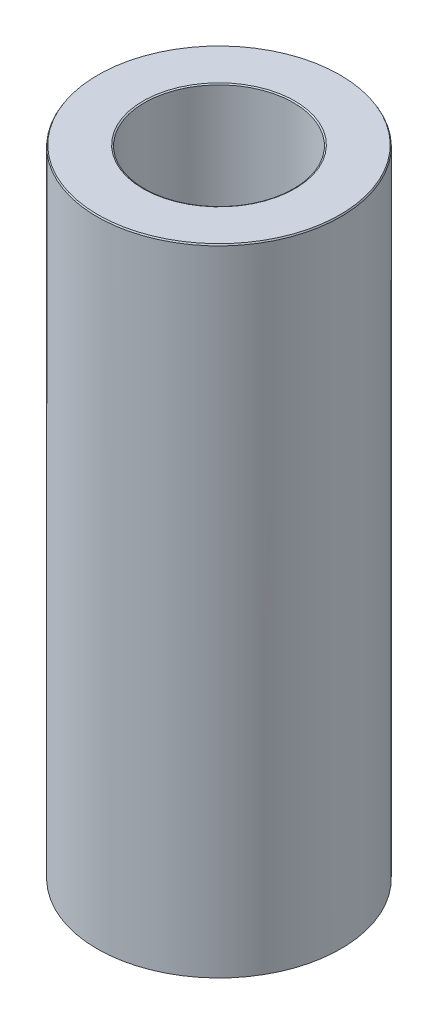
SolidWorks part; units mm, degrees
ref_plane "Front Plane" through (0, 0, 0) normal (0, 0, 1) x (1, 0, 0)
ref_plane "Top Plane" through (0, 0, 0) normal (0, 1, 0) x (1, 0, 0)
ref_plane "Right Plane" through (0, 0, 0) normal (1, 0, 0) x (0, 0, -1)
sketch "Sketch1" plane through (0, 0, 0) normal (0, 1, 0) x (1, 0, 0)
  circle A0 centre (0, 0) radius 57.5
  dimension "SLEEVE_OD" = 115
extrude "Boss-Extrude1" add sketch "Sketch1" along normal blind 300.1562
sketch "Sketch2" plane through (0, 0, 0) normal (0, 1, 0) x (1, 0, 0)
  circle A0 centre (0, 0) radius 35.1883
  dimension "BORE_D" = 70.3765
extrude "Cut-Extrude1" cut sketch "Sketch2" along normal through all
chamfer "Chamfer1" distance 0.65 angle 30 4 edges at (0, 300.1562, 35.1883) (0, 0, 35.1883) (0, 0, 57.5) (0, 300.1562, 57.5) first distance on face at (0, 300.1562, 35.1883) first distance on face at (0, 0, 35.1883) first distance on face at (0, 300.1562, 57.5)
